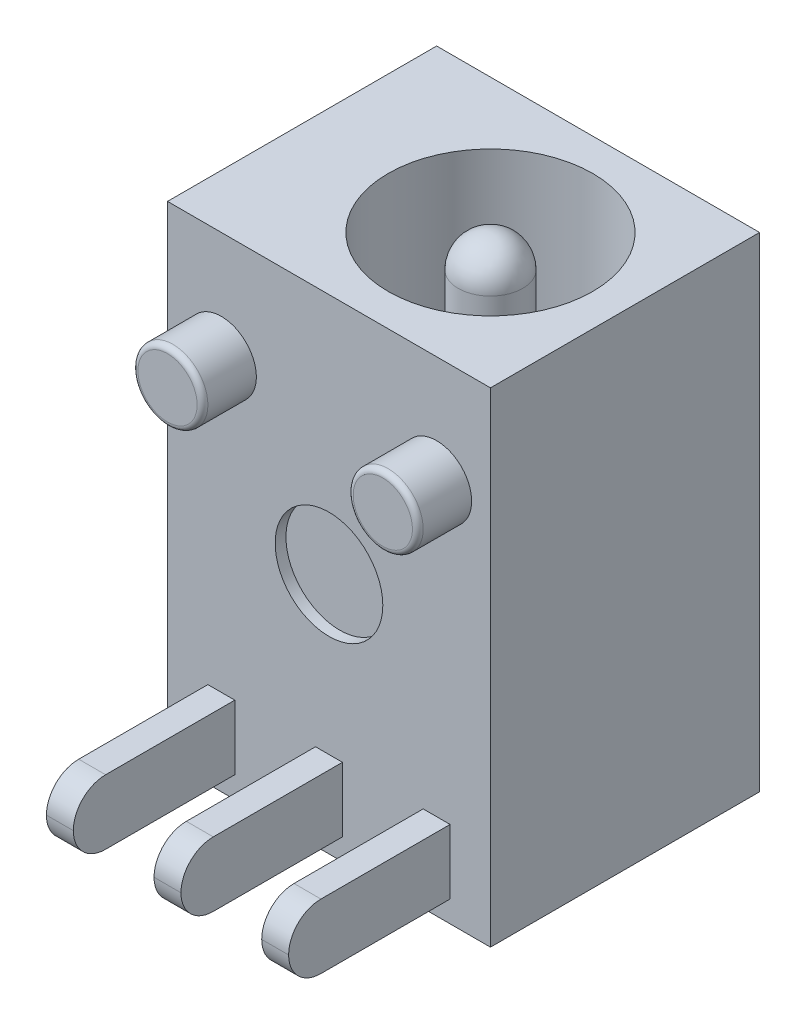
SolidWorks part; units mm, degrees
ref_plane "Front Plane" through (0, 0, 0) normal (0, 0, 1) x (1, 0, 0)
ref_plane "Top Plane" through (0, 0, 0) normal (0, 1, 0) x (1, 0, 0)
ref_plane "Right Plane" through (0, 0, 0) normal (1, 0, 0) x (0, 0, -1)
sketch "Sketch2" plane through (0, 0, 0) normal (0, 1, 0) x (1, 0, 0)
  line L1 (-3, -2.5) -> (3, -2.5)
  line L2 (-3, -2.5) -> (-3, 2.5)
  line L3 (-3, 2.5) -> (3, 2.5)
  line L4 (3, -2.5) -> (3, 2.5)
  line L5 (-3, -2.5) -> (3, 2.5) construction
  line L6 (-3, 2.5) -> (3, -2.5) construction
  point P0 (0, 0)
  dimension "D1" = 6
  dimension "D2" = 5
extrude "Boss-Extrude1" add sketch "Sketch2" along normal blind 9
sketch "Sketch3" plane through (0, 9, 0) normal (0, 1, 0) x (1, 0, 0)
  line L0 (0.5, 2.5) -> (0.5, -2.5) construction
  line L1 (3, 2.5) -> (-3, 2.5) construction
  line L2 (-3, -2.5) -> (3, -2.5) construction
  line L3 (-3, 2.5) -> (-3, -2.5) construction
  circle A0 centre (0.5, 0) radius 1.9
  circle A1 centre (0.5, 0) radius 0.6
  dimension "D1" = 1.2
  dimension "D2" = 3.8
  dimension "D3" = 3.5
extrude "Cut-Extrude1" cut sketch "Sketch3" against normal blind 7
fillet "Fillet1" radius 0.6 1 edges at (0.5, 9, 0.6)
sketch "Sketch4" plane through (0, 0, 2.5) normal (0, 0, 1) x (1, 0, 0)
  line L0 (3, 7.4511) -> (-3, 7.4511) construction
  line L1 (3, 9) -> (3, 0) construction
  line L2 (-3, 9) -> (-3, 0) construction
  line L3 (3, 1) -> (-3, 1) construction
  line L4 (-3, 9) -> (3, 9) construction
  line L5 (2.25, 1.6) -> (1.75, 1.6)
  line L6 (2.25, 1.6) -> (2.25, 0.4)
  line L7 (2.25, 0.4) -> (1.75, 0.4)
  line L8 (1.75, 1.6) -> (1.75, 0.4)
  line L9 (2.25, 1.6) -> (1.75, 0.4) construction
  line L10 (2.25, 0.4) -> (1.75, 1.6) construction
  line L11 (0.25, 0.4) -> (-0.25, 0.4)
  line L12 (0.25, 0.4) -> (0.25, 1.6)
  line L13 (0.25, 1.6) -> (-0.25, 1.6)
  line L14 (-0.25, 0.4) -> (-0.25, 1.6)
  line L15 (0.25, 0.4) -> (-0.25, 1.6) construction
  line L16 (0.25, 1.6) -> (-0.25, 0.4) construction
  line L17 (-1.75, 0.4) -> (-2.25, 0.4)
  line L18 (-1.75, 0.4) -> (-1.75, 1.6)
  line L19 (-1.75, 1.6) -> (-2.25, 1.6)
  line L20 (-2.25, 0.4) -> (-2.25, 1.6)
  line L21 (-1.75, 0.4) -> (-2.25, 1.6) construction
  line L22 (-1.75, 1.6) -> (-2.25, 0.4) construction
  point P8 (2, 1)
  point P13 (0, 1)
  point P18 (-2, 1)
  dimension "D1" = 1.2
  dimension "D2" = 0.5
  dimension "D3" = 4
  dimension "D4" = 2
  dimension "D5" = 8
extrude "Boss-Extrude2" add sketch "Sketch4" along normal blind 3
fillet "Fillet2" radius 0.6 6 edges at (-2, 0.4, 5.5) (-2, 1.6, 5.5) (0, 1.6, 5.5) (0, 0.4, 5.5) (2, 0.4, 5.5) (2, 1.6, 5.5)
sketch "Sketch5" plane through (0, 0, 2.5) normal (0, 0, 1) x (1, 0, 0)
  line L0 (3, 7) -> (-3, 7) construction
  line L1 (3, 9) -> (3, 0) construction
  line L2 (-3, 9) -> (-3, 0) construction
  line L3 (-3, 9) -> (3, 9) construction
  line L4 (2, 1.6) -> (2, 7) construction
  line L5 (2.25, 1.6) -> (1.75, 1.6) construction
  line L6 (-2, 1.6) -> (-2, 7) construction
  line L7 (-1.75, 1.6) -> (-2.25, 1.6) construction
  circle A0 centre (2, 7) radius 0.65
  circle A1 centre (-2, 7) radius 0.65
  dimension "D2" = 1.3
  dimension "D1" = 2
extrude "Boss-Extrude3" add sketch "Sketch5" along normal blind 1
fillet "Fillet3" radius 0.1 2 edges at (-1.35, 7, 3.5) (2.65, 7, 3.5)
sketch "Sketch6" plane through (0, 0, 2.5) normal (0, 0, 1) x (1, 0, 0)
  line L0 (0, 9) -> (0, 0) construction
  line L1 (-3, 9) -> (3, 9) construction
  line L2 (-3, 0) -> (3, 0) construction
  circle A0 centre (0, 4.5) radius 1
  dimension "D1" = 2
extrude "Cut-Extrude2" cut sketch "Sketch6" against normal blind 0.2
